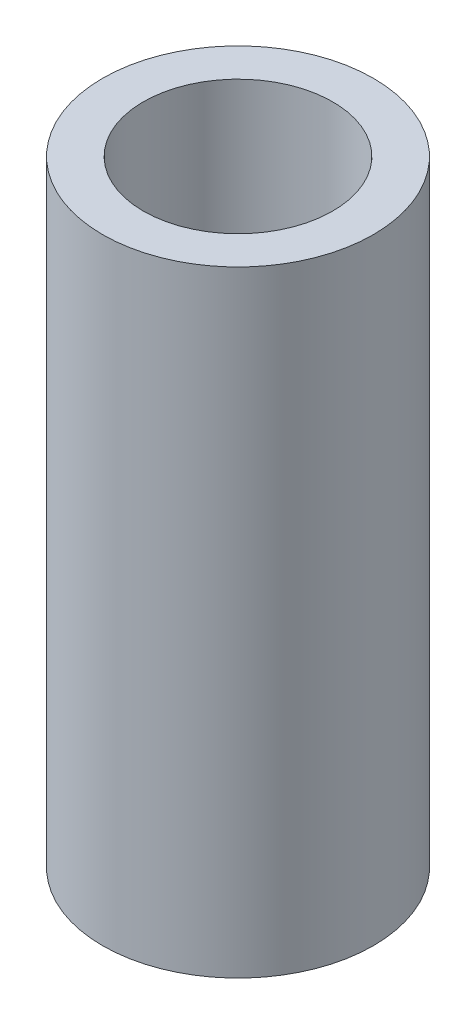
SolidWorks part; units mm, degrees
ref_plane "Front Plane" through (0, 0, 0) normal (0, 0, 1) x (1, 0, 0)
ref_plane "Top Plane" through (0, 0, 0) normal (0, 1, 0) x (1, 0, 0)
ref_plane "Right Plane" through (0, 0, 0) normal (1, 0, 0) x (0, 0, -1)
sketch "Sketch1" plane through (0, 0, 0) normal (0, 1, 0) x (1, 0, 0)
  circle A0 centre (0, 0) radius 25
  dimension "SLEEVE_OD" = 50
extrude "Boss-Extrude1" add sketch "Sketch1" along normal blind 113.7042
sketch "Sketch2" plane through (0, 0, 0) normal (0, 1, 0) x (1, 0, 0)
  circle A0 centre (0, 0) radius 17.4836
  dimension "BORE_D" = 34.9673
extrude "Cut-Extrude1" cut sketch "Sketch2" along normal through all
chamfer "Chamfer1" distance 3.7133 angle 57.389 rebuild error yes
